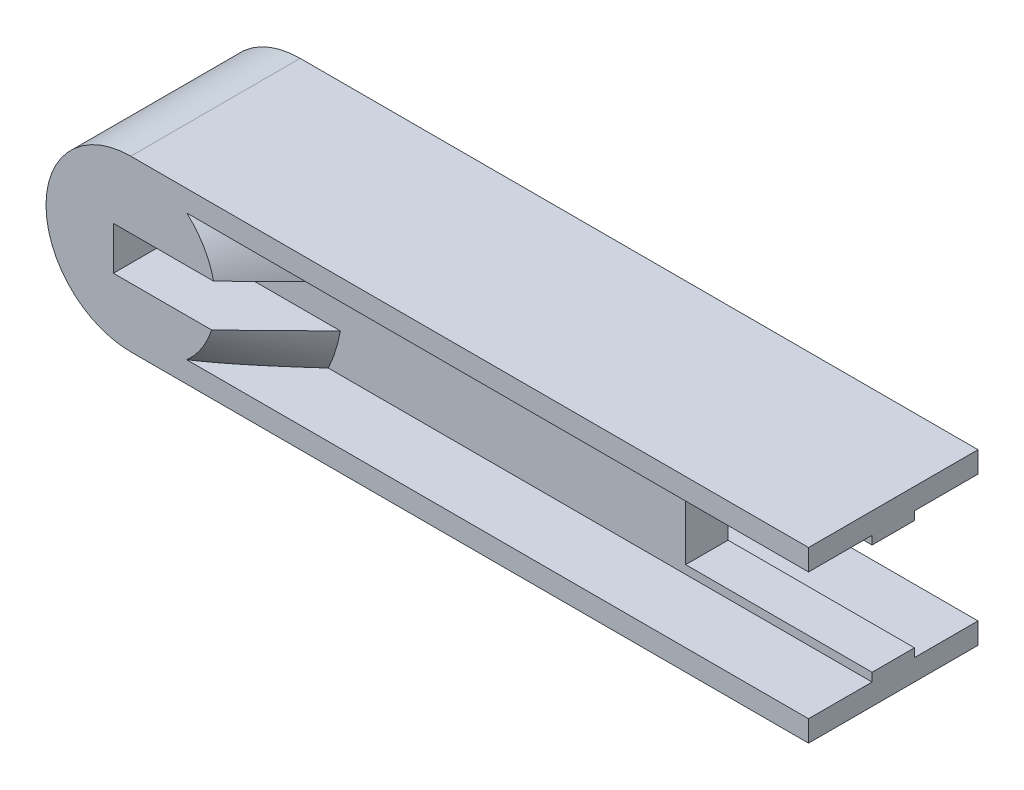
SolidWorks part; units mm, degrees
ref_plane "Front Plane" through (0, 0, 0) normal (0, 0, 1) x (1, 0, 0)
ref_plane "Top Plane" through (0, 0, 0) normal (0, 1, 0) x (1, 0, 0)
ref_plane "Right Plane" through (0, 0, 0) normal (1, 0, 0) x (0, 0, -1)
sketch "Sketch1" plane through (0, 0, 0) normal (0, 1, 0) x (1, 0, 0)
  line L0 (-40, -10) -> (-40, 10)
  line L1 (-40, -10) -> (40, -10)
  line L2 (-40, 10) -> (40, 10)
  line L3 (40, -10) -> (40, 10)
  line L4 (-40, -10) -> (40, 10) construction
  line L5 (-40, 10) -> (40, -10) construction
  point P1 (0, 0)
  dimension "D1" = 80
  dimension "D2" = 20
extrude "Boss-Extrude1" add sketch "Sketch1" along normal mid plane 20
sketch "Sketch2" plane through (0, 0, 0) normal (0, 1, 0) x (1, 0, 0)
  line L0 (40, 10) -> (40, 2.5)
  line L1 (40, -10) -> (-40, -10)
  line L2 (-40, -10) -> (-40, -2.5)
  line L3 (-40, 10) -> (40, 10)
  line L4 (-40, 2.5) -> (40, 2.5)
  line L6 (40, -2.5) -> (-40, -2.5)
  line L8 (0, 2.5) -> (0, -2.5) construction
  line L9 (-40, 2.5) -> (-40, 10)
  line L10 (40, -2.5) -> (40, -10)
  point P14 (0, 0)
  dimension "D1" = 5
extrude "Cut-Extrude1" cut sketch "Sketch2" against normal mid plane 15
sketch "Sketch3" plane through (0, 0, 0) normal (0, 0, 1) x (1, 0, 0)
  line L20 (-40, -7.5) -> (-40, 7.5) construction
  circle A5 centre (-40, 0) radius 10
extrude "Boss-Extrude2" add sketch "Sketch3" along normal mid plane 20
chamfer "Chamfer1" distance 7.5 angle 45 2 edges at (-30, 0, -2.5) (-30, 0, 2.5)
sketch "Sketch8" plane through (0, 0, 10) normal (0, 0, 1) x (1, 0, 0)
  line L5 (-42.0429, 2.1132) -> (-17.642, 2.1132)
  line L6 (-42.0429, 2.1132) -> (-42.0429, -2.9888)
  line L7 (-42.0429, -2.9888) -> (-17.642, -2.9888)
  line L8 (-17.642, 2.1132) -> (-17.642, -2.9888)
extrude "Cut-Extrude2" cut sketch "Sketch8" against normal up to surface (7.5 mm away) up to face at (8.3278, 0, 2.5)
sketch "Sketch9" plane through (0, 0, -10) normal (0, 0, -1) x (-1, 0, 0)
  circle A0 centre (40, 0) radius 3.8
  dimension "D1" = 7.6
extrude "Cut-Extrude3" cut sketch "Sketch9" against normal blind 5
sketch "Sketch10" plane through (0, 0, -2.5) normal (0, 0, -1) x (-1, 0, 0)
  line L0 (-40, -7.5) -> (-40, 7.5) construction
  line L1 (-40, 6.5) -> (-18, 6.5)
  line L2 (-40, 6.5) -> (-40, -6.5)
  line L3 (-40, -6.5) -> (-18, -6.5)
  line L4 (-18, 6.5) -> (-18, -6.5)
  line L5 (-40, -7.5) -> (-40, 7.5) construction
  line L6 (22.5, 0) -> (-46.3308, 0) construction
  arc A0 (24.1886, 7.5) -> (24.1886, -7.5) centre (40, 0) ccw construction
  point P9 (-40, 0)
  point P16 (-18, 0)
  dimension "D1" = 22
  dimension "D2" = 13
extrude "Cut-Extrude4" cut sketch "Sketch10" against normal up to next
